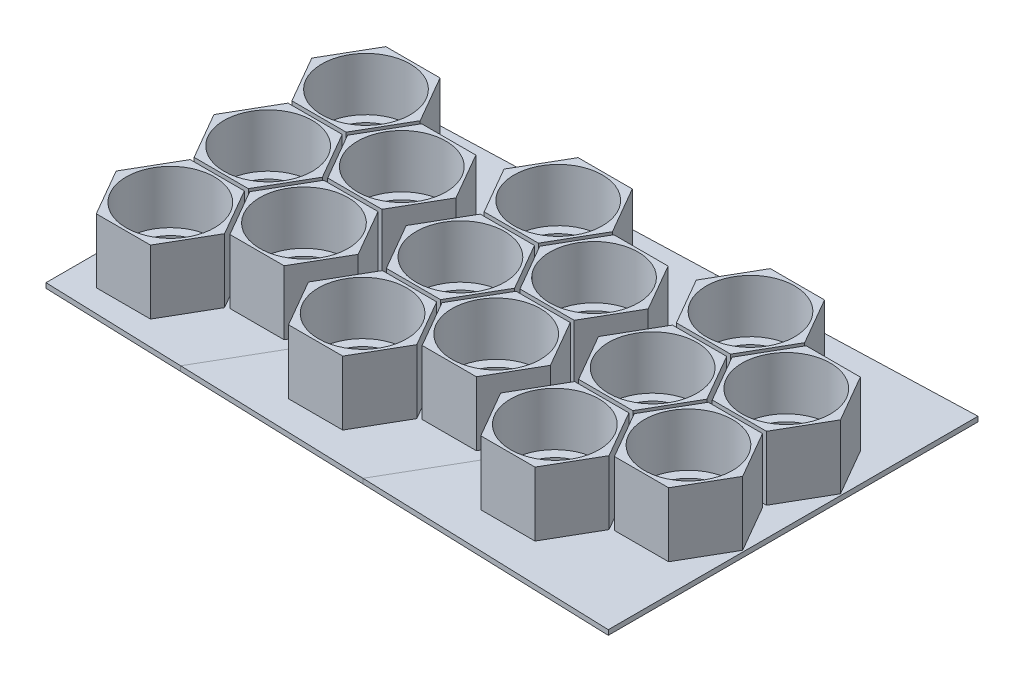
SolidWorks part; units mm, degrees
ref_plane "Front Plane" through (0, 0, 0) normal (0, 0, 1) x (1, 0, 0)
ref_plane "Top Plane" through (0, 0, 0) normal (0, 1, 0) x (1, 0, 0)
ref_plane "Right Plane" through (0, 0, 0) normal (1, 0, 0) x (0, 0, -1)
sketch "Sketch1" plane through (0, 0, 0) normal (0, 1, 0) x (1, 0, 0)
  line L0 (-118, 0) -> (118, 0)
  line L1 (-118, -67.135) -> (-118, 67.135)
  line L2 (118, -75) -> (118, 75)
  line L3 (-118, 67.135) -> (118, 75)
  line L4 (118, -75) -> (-118, -67.135)
  point P4 (0, 0)
  point P8 (-118, 0)
  point P11 (118, 0)
  dimension "D1" = 236
  dimension "D2" = 150
  dimension "D3" = 134.27
extrude "Boss-Extrude1" add sketch "Sketch1" along normal mid plane 2 contours L4 L2 L0 L1 | L3 L1 L0 L2 region at (2.1765, 0, -35.57) region at (2.1765, 0, 35.57)
sketch "Sketch3" plane through (0, 1, 0) normal (0, 1, 0) x (1, 0, 0)
  line L1 (-84.0015, 58.7375) -> (-105.9985, 58.7375)
  line L2 (-105.9985, 58.7375) -> (-116.997, 39.6875)
  line L3 (-116.997, 39.6875) -> (-105.9985, 20.6375)
  line L4 (-105.9985, 20.6375) -> (-84.0015, 20.6375)
  line L5 (-84.0015, 20.6375) -> (-73.003, 39.6875)
  line L6 (-73.003, 39.6875) -> (-84.0015, 58.7375)
  line L7 (-84.0015, 19.05) -> (-105.9985, 19.05)
  line L8 (-105.9985, 19.05) -> (-116.997, 0)
  line L9 (-116.997, 0) -> (-105.9985, -19.05)
  line L10 (-105.9985, -19.05) -> (-84.0015, -19.05)
  line L11 (-84.0015, -19.05) -> (-73.003, 0)
  line L12 (-73.003, 0) -> (-84.0015, 19.05)
  line L13 (-73.003, -39.6875) -> (-84.0015, -20.6375)
  line L14 (-84.0015, -20.6375) -> (-105.9985, -20.6375)
  line L15 (-105.9985, -20.6375) -> (-116.997, -39.6875)
  line L16 (-116.997, -39.6875) -> (-105.9985, -58.7375)
  line L17 (-105.9985, -58.7375) -> (-84.0015, -58.7375)
  line L18 (-84.0015, -58.7375) -> (-73.003, -39.6875)
  line L31 (-95, -19.05) -> (-95, -20.6375) construction
  line L32 (-105.9985, -58.7375) -> (-116.997, -39.6875)
  line L33 (-73.003, -39.6875) -> (-84.0015, -58.7375)
  line L34 (-84.0015, -20.6375) -> (-73.003, -39.6875)
  line L35 (-116.997, -39.6875) -> (-105.9985, -20.6375)
  line L36 (-116.997, 0) -> (-105.9985, 19.05)
  line L37 (-105.9985, -19.05) -> (-116.997, 0)
  line L38 (-73.003, 0) -> (-84.0015, -19.05)
  line L39 (-84.0015, 19.05) -> (-73.003, 0)
  line L40 (-116.997, 39.6875) -> (-105.9985, 58.7375)
  line L41 (-105.9985, 20.6375) -> (-116.997, 39.6875)
  line L42 (-73.003, 39.6875) -> (-84.0015, 20.6375)
  line L43 (-84.0015, 58.7375) -> (-73.003, 39.6875)
  line L44 (-105.9985, 58.7375) -> (-116.997, 39.6875)
  line L45 (-116.997, 39.6875) -> (-105.9985, 20.6375)
  line L46 (-84.0015, 20.6375) -> (-73.003, 39.6875)
  line L47 (-73.003, 39.6875) -> (-84.0015, 58.7375)
  line L48 (-105.9985, 19.05) -> (-116.997, 0)
  line L49 (-116.997, 0) -> (-105.9985, -19.05)
  line L50 (-84.0015, -19.05) -> (-73.003, 0)
  line L51 (-73.003, 0) -> (-84.0015, 19.05)
  line L52 (-73.003, -39.6875) -> (-84.0015, -20.6375)
  line L53 (-105.9985, -20.6375) -> (-116.997, -39.6875)
  line L54 (-116.997, -39.6875) -> (-105.9985, -58.7375)
  line L55 (-84.0015, -58.7375) -> (-73.003, -39.6875)
  line L56 (-105.9985, -58.7375) -> (-116.997, -39.6875)
  line L57 (-73.003, -39.6875) -> (-84.0015, -58.7375)
  line L58 (-84.0015, -20.6375) -> (-73.003, -39.6875)
  line L59 (-116.997, -39.6875) -> (-105.9985, -20.6375)
  line L60 (-116.997, 0) -> (-105.9985, 19.05)
  line L61 (-105.9985, -19.05) -> (-116.997, 0)
  line L62 (-73.003, 0) -> (-84.0015, -19.05)
  line L63 (-84.0015, 19.05) -> (-73.003, 0)
  line L64 (-116.997, 39.6875) -> (-105.9985, 58.7375)
  line L65 (-105.9985, 20.6375) -> (-116.997, 39.6875)
  line L66 (-73.003, 39.6875) -> (-84.0015, 20.6375)
  line L67 (-84.0015, 58.7375) -> (-73.003, 39.6875)
  line L68 (-105.9985, 58.7375) -> (-116.997, 39.6875)
  line L69 (-116.997, 39.6875) -> (-105.9985, 20.6375)
  line L70 (-84.0015, 20.6375) -> (-73.003, 39.6875)
  line L71 (-73.003, 39.6875) -> (-84.0015, 58.7375)
  line L72 (-105.9985, 19.05) -> (-116.997, 0)
  line L73 (-116.997, 0) -> (-105.9985, -19.05)
  line L74 (-84.0015, -19.05) -> (-73.003, 0)
  line L75 (-73.003, 0) -> (-84.0015, 19.05)
  line L76 (-73.003, -39.6875) -> (-84.0015, -20.6375)
  line L77 (-105.9985, -20.6375) -> (-116.997, -39.6875)
  line L78 (-116.997, -39.6875) -> (-105.9985, -58.7375)
  line L79 (-84.0015, -58.7375) -> (-73.003, -39.6875)
  line L80 (-105.9985, -58.7375) -> (-116.997, -39.6875)
  line L81 (-73.003, -39.6875) -> (-84.0015, -58.7375)
  line L82 (-84.0015, -20.6375) -> (-73.003, -39.6875)
  line L83 (-116.997, -39.6875) -> (-105.9985, -20.6375)
  line L84 (-116.997, 0) -> (-105.9985, 19.05)
  line L85 (-105.9985, -19.05) -> (-116.997, 0)
  line L86 (-73.003, 0) -> (-84.0015, -19.05)
  line L87 (-84.0015, 19.05) -> (-73.003, 0)
  line L88 (-116.997, 39.6875) -> (-105.9985, 58.7375)
  line L89 (-105.9985, 20.6375) -> (-116.997, 39.6875)
  line L90 (-73.003, 39.6875) -> (-84.0015, 20.6375)
  line L91 (-84.0015, 58.7375) -> (-73.003, 39.6875)
  line L92 (-105.9985, 58.7375) -> (-116.997, 39.6875)
  line L93 (-116.997, 39.6875) -> (-105.9985, 20.6375)
  line L94 (-84.0015, 20.6375) -> (-73.003, 39.6875)
  line L95 (-73.003, 39.6875) -> (-84.0015, 58.7375)
  line L96 (-105.9985, 19.05) -> (-116.997, 0)
  line L97 (-116.997, 0) -> (-105.9985, -19.05)
  line L98 (-84.0015, -19.05) -> (-73.003, 0)
  line L99 (-73.003, 0) -> (-84.0015, 19.05)
  line L100 (-73.003, -39.6875) -> (-84.0015, -20.6375)
  line L101 (-105.9985, -20.6375) -> (-116.997, -39.6875)
  line L102 (-116.997, -39.6875) -> (-105.9985, -58.7375)
  line L103 (-84.0015, -58.7375) -> (-73.003, -39.6875)
  line L104 (-105.9985, -58.7375) -> (-116.997, -39.6875)
  line L105 (-73.003, -39.6875) -> (-84.0015, -58.7375)
  line L106 (-84.0015, -20.6375) -> (-73.003, -39.6875)
  line L107 (-116.997, -39.6875) -> (-105.9985, -20.6375)
  line L108 (-116.997, 0) -> (-105.9985, 19.05)
  line L109 (-105.9985, -19.05) -> (-116.997, 0)
  line L110 (-73.003, 0) -> (-84.0015, -19.05)
  line L111 (-84.0015, 19.05) -> (-73.003, 0)
  line L112 (-116.997, 39.6875) -> (-105.9985, 58.7375)
  line L113 (-105.9985, 20.6375) -> (-116.997, 39.6875)
  line L114 (-73.003, 39.6875) -> (-84.0015, 20.6375)
  line L115 (-84.0015, 58.7375) -> (-73.003, 39.6875)
  line L135 (-95, 20.6375) -> (-95, 19.05) construction
  line L136 (-78.5022, -9.525) -> (-77.1274, -10.3188) construction
  line L138 (0, 0) -> (-118, 0) construction
  line L139 (-118, -67.135) -> (-118, 67.135) construction
  line L140 (-49.6311, 38.8937) -> (-38.6326, 19.8438)
  line L141 (-38.6326, -19.8438) -> (-49.6311, -0.7938)
  line L142 (-49.6311, -0.7938) -> (-71.6281, -0.7938)
  line L143 (-71.6281, -0.7938) -> (-82.6267, -19.8438)
  line L144 (-82.6267, -19.8438) -> (-71.6281, -38.8938)
  line L145 (-71.6281, -38.8938) -> (-49.6311, -38.8938)
  line L146 (-49.6311, -38.8938) -> (-38.6326, -19.8438)
  line L147 (-71.6281, 38.8937) -> (-49.6311, 38.8937)
  line L148 (-82.6267, 19.8438) -> (-71.6281, 38.8937)
  line L149 (-71.6281, 0.7937) -> (-82.6267, 19.8438)
  line L150 (-49.6311, 0.7938) -> (-71.6281, 0.7937)
  line L151 (-38.6326, 19.8438) -> (-49.6311, 0.7938)
  circle A0 centre (-95, 39.6875) radius 19.05 construction
  circle A1 centre (-95, 0) radius 19.05 construction
  circle A2 centre (-95, -39.6875) radius 19.05 construction
  circle A3 centre (-60.6296, -19.8438) radius 19.05 construction
  dimension "D1" = 38.1
  dimension "D3" = 23
  dimension "D2" = 1.5875
extrude "Boss-Extrude2" add sketch "Sketch3" along normal blind 26 contours L5 L6 L1 L2 L3 L4 | L151 L140 L147 L148 L149 L150 | L11 L12 L7 L8 L9 L10 | L17 L18 L13 L14 L15 L16 | L145 L146 L141 L142 L143 L144 region at (-95, 1, -39.6875) region at (-95, 1, 0) region at (-95, 1, 39.6875) region at (-60.6296, 1, -19.8437) region at (-60.6296, 1, 19.8438)
sketch "Sketch4" plane through (0, 27, 0) normal (0, 1, 0) x (1, 0, 0)
  line L0 (-116.997, 0) -> (-73.003, 0) construction
  line L2 (-116.997, -39.6875) -> (-73.003, -39.6875) construction
  line L3 (-82.6267, 19.8437) -> (-38.6326, 19.8438) construction
  circle A0 centre (-95, 0) radius 13.97
  circle A1 centre (-95, 0) radius 17.907
  circle A2 centre (-95, -39.6875) radius 13.97
  circle A3 centre (-95, -39.6875) radius 17.907
  circle A4 centre (-95, 39.6875) radius 13.97
  circle A5 centre (-95, 39.6875) radius 17.907
  circle A6 centre (-60.6296, 19.8437) radius 13.97
  circle A7 centre (-60.6296, 19.8437) radius 17.907
  circle A8 centre (-60.6296, -19.8437) radius 17.907
  circle A9 centre (-60.6296, -19.8437) radius 13.97
  dimension "D1" = 27.94
  dimension "D2" = 35.814
extrude "Cut-Extrude1" cut sketch "Sketch4" against normal blind 25.4 contours A2 | A0 | A9 | A6 | A4
extrude "Cut-Extrude2" cut sketch "Sketch4<4>" against normal blind 21.5544 contours A3 | A1 | A8 | A7 | A5
sketch "Sketch4<4>" plane through (0, 27, 0) normal (0, 1, 0) x (1, 0, 0) same geometry as "Sketch4"
pattern_linear "LPattern1" count 3 spacing 78 along (1, 0, 0) of "Boss-Extrude2", "Cut-Extrude1", "Cut-Extrude2"
sketch "Sketch9" plane through (0, 1, 0) normal (0, 1, 0) x (1, 0, 0)
  line L0 (-39.6981, -21.6892) -> (-31.3788, -26.4924) construction
  line L1 (-49.6311, -38.8938) -> (-38.6326, -19.8438) construction
  line L2 (-27.9985, -20.6375) -> (-38.997, -39.6875) construction
  line L3 (-35.5722, -5.932) -> (-43.8914, -10.7352) construction
  line L4 (-38.997, 0) -> (-27.9985, -19.05) construction
  line L5 (-38.6326, -19.8438) -> (-49.6311, -0.7938) construction
  line L6 (-44.1318, 10.3187) -> (-35.8126, 5.5156) construction
  line L7 (-38.6326, 19.8438) -> (-49.6311, 0.7938) construction
  line L8 (-27.9985, 19.05) -> (-38.997, 0) construction
  line L9 (-44.1318, 29.3688) -> (-35.8126, 34.1719) construction
  line L11 (-38.997, 39.6875) -> (-27.9985, 20.6375) construction
  line L12 (-39.9722, 31.7703) -> (-33.0864, 19.8437)
  line L13 (-39.9722, 7.9172) -> (-33.0864, 19.8437)
  line L14 (-39.9722, 7.9172) -> (-44.5432, 0)
  line L15 (-49.6311, 38.8937) -> (-38.6326, 19.8438) construction
  line L16 (-38.997, 39.6875) -> (-27.9985, 20.6375) construction
  line L17 (-27.9985, 19.05) -> (-38.997, 0) construction
  line L18 (-39.7318, -8.3336) -> (-44.5432, 0)
  line L19 (-35.5384, -24.0908) -> (-33.0864, -19.8438)
  line L20 (-39.7318, -8.3336) -> (-33.0864, -19.8438)
  line L21 (-38.6326, -19.8438) -> (-49.6311, -0.7938) construction
  line L22 (-39.9722, 31.7703) -> (-61.4776, 69.0187)
  line L23 (-118, 67.135) -> (118, 75) construction
  line L24 (-35.5384, -24.0908) -> (-61.4776, -69.0187)
  line L25 (118, -75) -> (-118, -67.135) construction
  line L26 (37.81, 22.5413) -> (46.1292, 27.3444) construction
  line L27 (28.3689, 38.8937) -> (39.3674, 19.8438) construction
  line L28 (39.003, 39.6875) -> (50.0015, 20.6375) construction
  line L30 (33.8682, 10.3188) -> (42.1874, 5.5156) construction
  line L31 (50.0015, 19.05) -> (39.003, 0) construction
  line L32 (47.6867, -15.0406) -> (39.3674, -19.8438) construction
  line L33 (39.003, 0) -> (50.0015, -19.05) construction
  line L34 (39.3674, -19.8438) -> (28.3689, -0.7938) construction
  line L35 (39.3674, -19.8438) -> (28.3689, -0.7938) construction
  line L36 (33.8682, -29.3687) -> (42.1874, -34.1719) construction
  line L38 (50.0015, -20.6375) -> (39.003, -39.6875) construction
  line L39 (28.3689, 38.8937) -> (39.3674, 19.8438) construction
  line L40 (39.3674, 19.8438) -> (28.3689, 0.7938) construction
  line L41 (39.3674, 19.8438) -> (28.3689, 0.7938) construction
  line L42 (28.3689, -38.8938) -> (39.3674, -19.8438) construction
  line L43 (41.9696, 24.9429) -> (15.05, 71.5691)
  line L44 (41.9696, 24.9429) -> (44.9136, 19.8438)
  line L45 (38.0278, 7.9172) -> (44.9136, 19.8438)
  line L46 (38.0278, 7.9172) -> (33.4568, 0)
  line L47 (33.4568, 0) -> (43.527, -17.4422)
  line L48 (43.527, -17.4422) -> (44.9136, -19.8437)
  line L49 (38.0278, -31.7703) -> (15.05, -71.5691)
  line L50 (44.9136, -19.8437) -> (38.0278, -31.7703)
  point P20 (0, 0)
  point P21 (0, 0)
  point P51 (0, 0)
  point P83 (0, 0)
split "Split3" trim tools "Sketch9" bodies to split 105 resulting bodies 113 114 115
delete or keep bodies "Body-Delete/Keep 1" [suppressed] type delete bodies bodies 113 114
delete or keep bodies "Body-Delete/Keep 2" [suppressed] type delete bodies bodies 114 115
delete or keep bodies "Body-Delete/Keep 3" [suppressed] type delete bodies bodies 113 115
